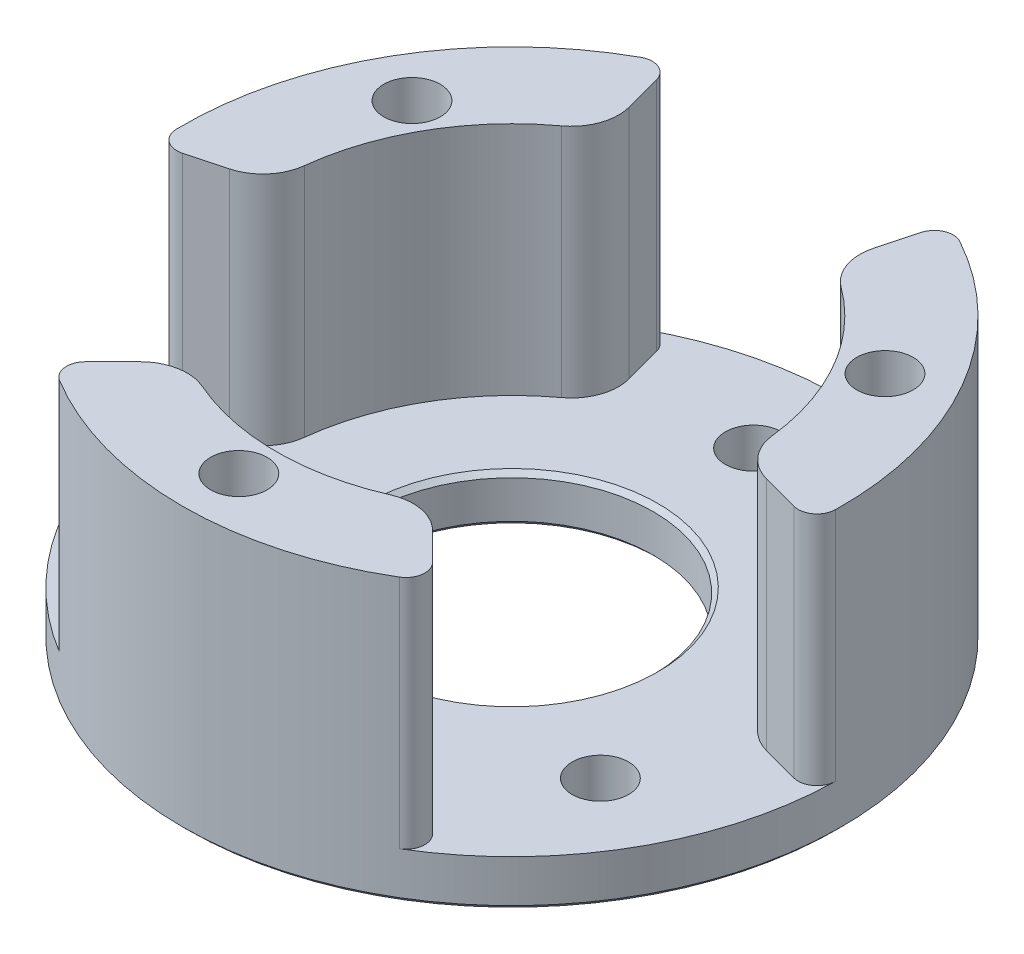
SolidWorks part; units mm, degrees
ref_plane "Front Plane" through (0, 0, 0) normal (0, 0, 1) x (1, 0, 0)
ref_plane "Top Plane" through (0, 0, 0) normal (0, 1, 0) x (1, 0, 0)
ref_plane "Right Plane" through (0, 0, 0) normal (1, 0, 0) x (0, 0, -1)
sketch "Sketch1" plane through (0, 0, 0) normal (0, 1, 0) x (1, 0, 0)
  line L0 (0, 25.66) -> (0, 0) construction
  line L1 (22.2222, -12.83) -> (0, 0) construction
  line L2 (-22.2222, -12.83) -> (0, 0) construction
  circle A0 centre (0, 0) radius 25.66 construction
  circle A1 centre (0, 0) radius 35
  circle A2 centre (0, 25.66) radius 3
  circle A3 centre (22.2222, -12.83) radius 3
  circle A4 centre (-22.2222, -12.83) radius 3
  circle A5 centre (0, 0) radius 15
  point P3 (0, 25.66)
  point P7 (22.2222, -12.83)
  point P9 (-22.2222, -12.83)
  point P11 (0, 0)
  point P18 (0, 0)
  dimension "D3" = 70
  dimension "D4" = 6
  dimension "D6" = 30
  dimension "D2" = 25.66
  dimension "D1" = 3
  dimension "D5" = 3
extrude "Boss-Extrude1" add sketch "Sketch1" along normal blind 5
sketch "Sketch2" plane through (0, 5, 0) normal (0, -1, 0) x (1, 0, 0)
  line L0 (0, 0) -> (0, 35) construction
  line L1 (15.5355, 23.9599) -> (20.1755, 28.5998)
  line L2 (-15.5355, 23.9599) -> (-20.1755, 28.5998)
  line L3 (28.5177, 1.4742) -> (34.8559, 3.1725)
  line L4 (12.9821, -25.4341) -> (14.6805, -31.7724)
  line L5 (-12.9821, -25.4341) -> (-14.6805, -31.7724)
  line L6 (-28.5177, 1.4742) -> (-34.8559, 3.1725)
  circle A0 centre (0, 0) radius 35 construction
  arc A1 (-20.1755, 28.5998) -> (20.1755, 28.5998) centre (0, 0) cw
  arc A2 (-10, 22.9129) -> (10, 22.9129) centre (0, 0) cw
  arc A3 (10, 22.9129) -> (15.5355, 23.9599) centre (12, 27.4955) ccw
  arc A4 (-10, 22.9129) -> (-15.5355, 23.9599) centre (-12, 27.4955) cw
  arc A5 (24.8431, -2.7962) -> (28.5177, 1.4742) centre (29.8118, -3.3554) cw
  arc A6 (34.8559, 3.1725) -> (14.6805, -31.7724) centre (0, 0) cw
  arc A7 (14.8431, -20.1167) -> (12.9821, -25.4341) centre (17.8118, -24.14) ccw
  arc A8 (24.8431, -2.7962) -> (14.8431, -20.1167) centre (0, 0) cw
  arc A9 (-14.8431, -20.1167) -> (-12.9821, -25.4341) centre (-17.8118, -24.14) cw
  arc A10 (-14.6805, -31.7724) -> (-34.8559, 3.1725) centre (0, 0) cw
  arc A11 (-24.8431, -2.7962) -> (-28.5177, 1.4742) centre (-29.8118, -3.3554) ccw
  arc A12 (-14.8431, -20.1167) -> (-24.8431, -2.7962) centre (0, 0) cw
  point P33 (0, 0)
  dimension "D1" = 5
  dimension "D2" = 25
  dimension "D3" = 45
  dimension "D4" = 20
  dimension "D5" = 3
extrude "Pegs" add sketch "Sketch2" against normal blind 24.9915
fillet "Fillet1" radius 2 6 edges at (-34.8559, 17.4958, 3.1725) (-14.6805, 17.4958, -31.7724) (14.6805, 17.4958, -31.7724) (34.8559, 17.4958, 3.1725) (20.1755, 17.4958, 28.5998) (-20.1755, 17.4958, 28.5998)
sketch "Sketch3" plane through (0, 0, 0) normal (0, -1, 0) x (1, 0, 0)
  line L0 (0, 0) -> (0, 29) construction
  line L1 (0, 0) -> (25.1147, -14.5) construction
  line L2 (0, 0) -> (-25.1147, -14.5) construction
  circle A0 centre (0, 0) radius 29 construction
  point P4 (0, 29)
  point P5 (25.1147, -14.5)
  point P7 (-25.1147, -14.5)
  point P8 (0, 0)
  dimension "D1" = 58
  dimension "D2" = 3
hole_wizard "Ø6.0mm Dowel Hole2" positions "Sketch3" profile "Sketch4" hole size "Ø6.0" standard "ANSI Metric" end condition through all
sketch "Sketch4" plane through (-25.1147, 0, -14.5) normal (1, 0, 0) x (0, 0, -1)
  line L0 (0, 0) -> (0, 29.9915)
  line L1 (0, 29.9915) -> (3, 29.9915)
  line L2 (3, 29.9915) -> (3, 0)
  line L5 (3, 0) -> (0, 0)
  line L11 (0, -6.35) -> (0, 107.95) construction
  dimension "Thru Hole Dia." = 6
  dimension "Thru Hole Depth" = 29.9915
sketch "Sketch5" plane through (0, 0, 0) normal (0, -1, 0) x (1, 0, 0)
  circle A0 centre (-25.1147, -14.5) radius 5
  circle A1 centre (0, 29) radius 5
  circle A2 centre (25.1147, -14.5) radius 5
  circle A3 centre (0, 0) radius 15 construction
  point P10 (0, 0)
  dimension "D1" = 10
  dimension "D2" = 3
extrude "Cut-Extrude1" cut sketch "Sketch5" against normal blind 2
chamfer "Chamfer1" distance 0.5 angle 45 3 edges at (0, 0, 35) (0, 0, 15) (0, 5, 15)
